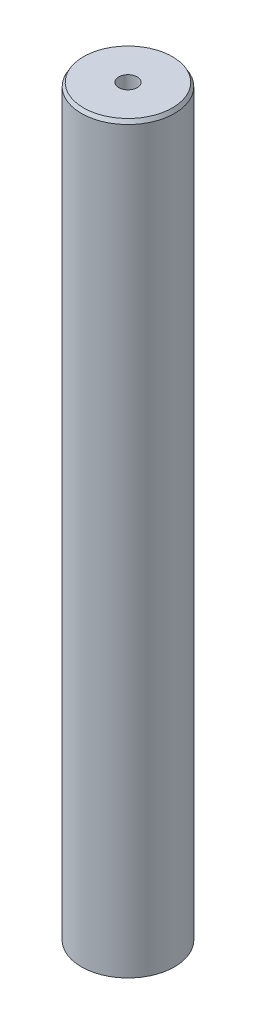
SolidWorks part; units mm, degrees
ref_plane "Front Plane" through (0, 0, 0) normal (0, 0, 1) x (1, 0, 0)
ref_plane "Top Plane" through (0, 0, 0) normal (0, 1, 0) x (1, 0, 0)
ref_plane "Right Plane" through (0, 0, 0) normal (1, 0, 0) x (0, 0, -1)
sketch "Sketch1" plane through (0, 0, 0) normal (0, 1, 0) x (1, 0, 0)
  circle A0 centre (0, 0) radius 25
  dimension "SHAFT_OD" = 50
extrude "Boss-Extrude1" add sketch "Sketch1" along normal blind 400
sketch "Sketch2" plane through (0, 0, 0) normal (0, 1, 0) x (1, 0, 0)
  circle A0 centre (0, 0) radius 5
  dimension "BORE_D" = 10
extrude "Cut-Extrude1" cut sketch "Sketch2" along normal through all
chamfer "Chamfer1" distance 2 angle 30 2 edges at (0, 400, 25) (0, 0, 25) first distance on face at (0, 400, 25) first distance on face at (0, 0, 5)
